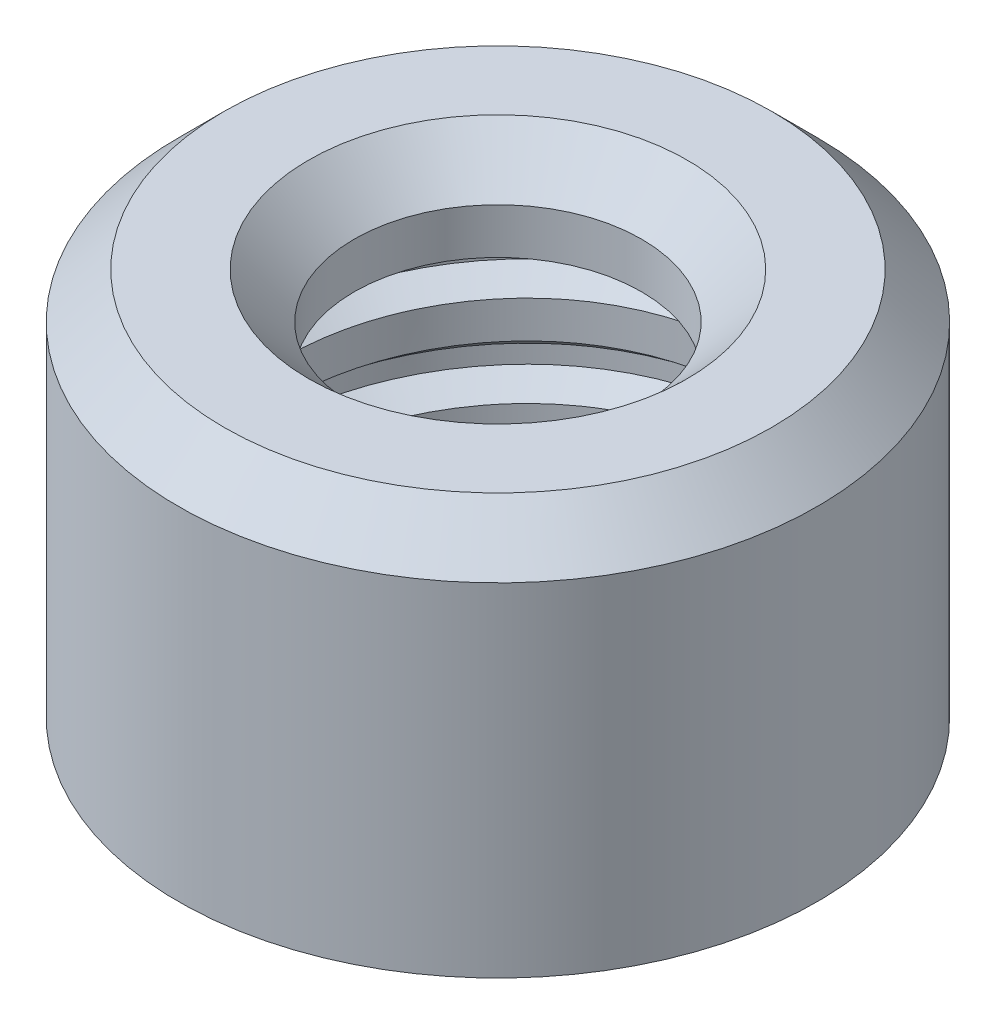
SolidWorks part; units mm, degrees
ref_plane "Front Plane" through (0, 0, 0) normal (0, 0, 1) x (1, 0, 0)
ref_plane "Top Plane" through (0, 0, 0) normal (0, 1, 0) x (1, 0, 0)
ref_plane "Right Plane" through (0, 0, 0) normal (1, 0, 0) x (0, 0, -1)
sketch "Sketch1" plane through (0, 0, 0) normal (0, 1, 0) x (1, 0, 0)
  circle A0 centre (0, 0) radius 5
  circle A1 centre (0, 0) radius 7
  dimension "D1" = 10
  dimension "D2" = 14
extrude "Boss-Extrude1" add sketch "Sketch1" along normal blind 6.5
sketch "Sketch2" plane through (0, 6.5, 0) normal (0, 1, 0) x (1, 0, 0)
  circle A1 centre (0, 0) radius 3.15
  circle A3 centre (0, 0) radius 7
  circle A4 centre (0, 0) radius 7
  dimension "D1" = 6.3
  dimension "D2" = 0
extrude "Boss-Extrude2" add sketch "Sketch2" along normal blind 2
chamfer "Chamfer1" distance 1 angle 45 1 edges at (0, 8.5, 3.15)
sketch "Sketch3" plane through (0, 6.5, 0) normal (0, -1, 0) x (1, 0, 0)
  circle A0 centre (0, 0) radius 5
  circle A1 centre (0, 0) radius 5 construction
curve "Helix/Spiral1" pitch 2 height 8 radius 5 left hand yes centre (0, 6.5, 0) axis (0, -1, 0) start towards (0, 0, -1)
ref_plane "Plane1" through (-3.5355, 6.5, 3.5355) normal (0.7057, -0.0635, 0.7057) x (0.7085, 0.0633, -0.7028)
sketch "Sketch4" plane through (-3.5355, 6.5, 3.5355) normal (0.7057, -0.0635, 0.7057) x (0.7085, 0.0633, -0.7028)
  line L0 (0.5784, 0.9637) -> (0.4389, -1.0314)
  line L1 (0.4389, -1.0314) -> (-0.5029, -0.1636)
  line L2 (-0.5029, -0.1636) -> (-0.475, 0.2354)
  line L3 (-0.475, 0.2354) -> (0.5784, 0.9637)
  line L4 (-0.4889, 0.0359) -> (0.5086, -0.0339) construction
  line L5 (0.406, 0.7048) -> (0.406, -0.8068) construction
  point P6 (0.406, 0.7048)
  point P7 (0.0051, -0.0008)
  point P8 (-0.0001, 0)
  point P9 (0, 0)
  point P10 (0, 0)
  point P11 (0, 0)
  point P12 (0.0272, -0.0012)
  point P13 (0.0382, -0.0032)
  point P14 (0.5104, -0.0384)
  point P15 (0.5086, -0.0339)
  dimension "D1" = 0.4
  dimension "D2" = 2
  dimension "D3" = 1
  dimension "D4" = 4
sweep "Cut-Sweep1" cut profiles "Sketch4" path "Helix/Spiral1" align with end faces yes
chamfer "Chamfer2" distance 1 angle 45 1 edges at (0, 8.5, 7)
